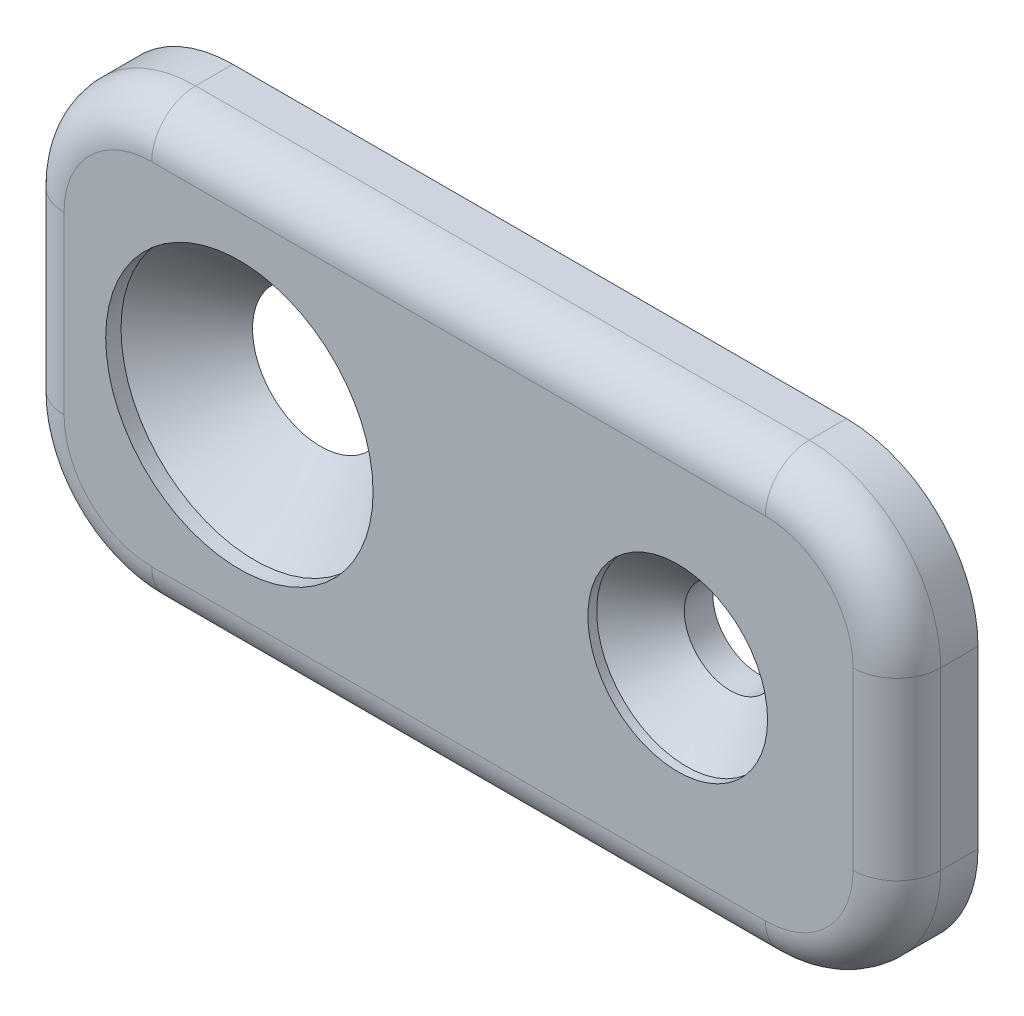
SolidWorks part; units mm, degrees
material "Custom Plastic"
ref_plane "Front Plane" through (0, 0, 0) normal (0, 0, 1) x (1, 0, 0)
ref_plane "Top Plane" through (0, 0, 0) normal (0, 1, 0) x (1, 0, 0)
ref_plane "Right Plane" through (0, 0, 0) normal (1, 0, 0) x (0, 0, -1)
sketch "Sketch1" plane through (0, 0, 0) normal (0, 0, 1) x (1, 0, 0)
  line L1 (30, 10) -> (-10, 10)
  line L2 (30, 10) -> (30, -10)
  line L3 (30, -10) -> (-10, -10)
  line L4 (-10, 10) -> (-10, -10)
  line L5 (30, 10) -> (-10, -10) construction
  line L6 (30, -10) -> (-10, 10) construction
  circle A0 centre (0, 0) radius 3.1
  circle A1 centre (20, 0) radius 2.1
  point P5 (10, 0)
  dimension "D1" = 6.2
  dimension "D4" = 4.2
  dimension "D5" = 20
  dimension "D2" = 10
  dimension "D3" = 20
  dimension "D6" = 40
extrude "Boss-Extrude1" add sketch "Sketch1" along normal blind 3.7
sketch "Sketch2" plane through (0, 0, 3.7) normal (0, 0, 1) x (1, 0, 0)
  circle A0 centre (0, 0) radius 6.1
  dimension "D1" = 12.2
extrude "Cut-Extrude1" cut sketch "Sketch2" against normal blind 0.7
chamfer "Chamfer1" distance 3 angle 45 1 edges at (3.1, 0, 3)
sketch "Sketch3" plane through (0, 0, 3.7) normal (0, 0, 1) x (1, 0, 0)
  circle A0 centre (20, 0) radius 4.1
  dimension "D1" = 8.2
extrude "Cut-Extrude2" cut sketch "Sketch3" against normal blind 0.4
chamfer "Chamfer2" distance 2 angle 45 1 edges at (22.1, 0, 3.3)
fillet "Fillet1" radius 6 4 edges at (30, -10, 1.85) (-10, -10, 1.85) (30, 10, 1.85) (-10, 10, 1.85)
fillet "Fillet2" radius 2 8 edges at (10, -10, 3.7) (28.2426, -8.2426, 3.7) (30, 0, 3.7) (28.2426, 8.2426, 3.7) (10, 10, 3.7) (-8.2426, 8.2426, 3.7) (-10, 0, 3.7) (-8.2426, -8.2426, 3.7)
